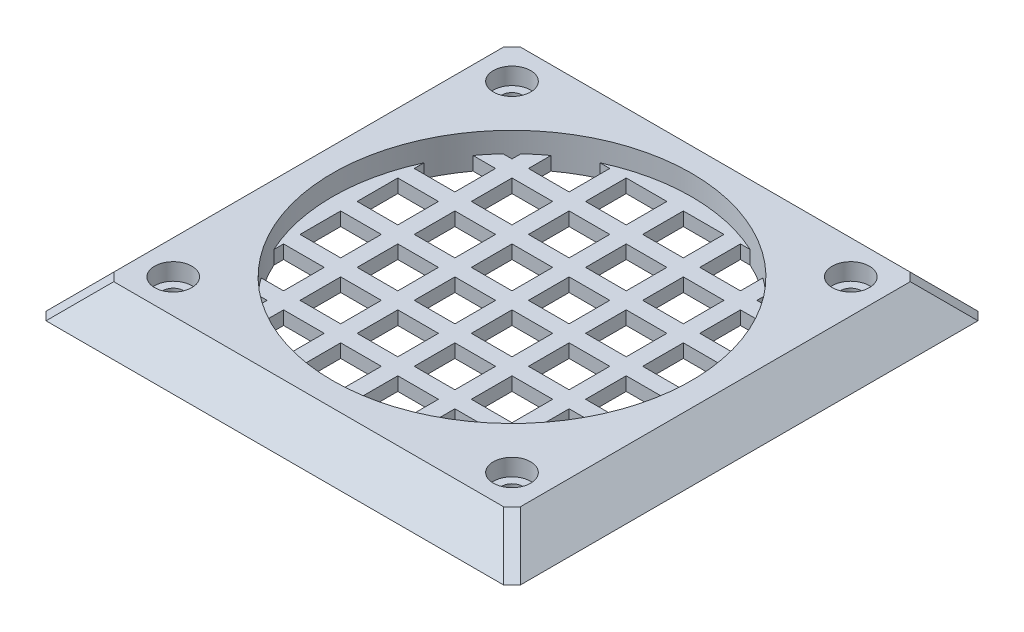
SolidWorks part; units mm, degrees
ref_plane "Front Plane" through (0, 0, 0) normal (0, 0, 1) x (1, 0, 0)
ref_plane "Top Plane" through (0, 0, 0) normal (0, 1, 0) x (1, 0, 0)
ref_plane "Right Plane" through (0, 0, 0) normal (1, 0, 0) x (0, 0, -1)
sketch "Sketch4" plane through (0, 0, 0) normal (0, 1, 0) x (1, 0, 0)
  line L1 (-57.895, 65.3251) -> (12.105, 65.3251)
  line L2 (-57.895, 65.3251) -> (-57.895, -4.6749)
  line L3 (-57.895, -4.6749) -> (12.105, -4.6749)
  line L4 (12.105, 65.3251) -> (12.105, -4.6749)
  dimension "D1" = 70
  dimension "D2" = 70
sketch "Sketch5" plane through (0, 0, 0) normal (0, 1, 0) x (1, 0, 0)
  line L0 (12.105, 65.3251) -> (12.105, -4.6749) construction
  line L1 (-57.895, 65.3251) -> (12.105, 65.3251) construction
  circle A0 centre (-22.895, 30.3251) radius 26.5
  dimension "D1" = 35
  dimension "D2" = 35
  dimension "D3" = 53
extrude "Boss-Extrude2" add sketch "Sketch4" against normal blind 5
extrude "Cut-Extrude3" cut sketch "Sketch5" against normal blind 3
chamfer "Chamfer2" distance 5 angle 45 1 edges at (12.105, 0, -30.3251)
chamfer "Chamfer3" distance 5 angle 45 1 edges at (-25.395, 0, -65.3251)
chamfer "Chamfer4" distance 5 angle 45 2 edges at (-25.395, 0, 4.6749) (-57.895, 0, -27.8251)
sketch "Sketch8" plane through (0, -3, 0) normal (0, 1, 0) x (1, 0, 0)
  line L0 (-49.395, 56.8251) -> (-46.9664, 56.8251)
  line L1 (-46.9664, 56.8251) -> (-46.9664, 54.3966)
  line L2 (-38.5379, 54.3966) -> (-38.5379, 48.3966)
  line L3 (-46.9664, 54.3966) -> (-40.9664, 54.3966)
  line L4 (-46.9664, 54.3966) -> (-46.9664, 48.3966)
  line L5 (-46.9664, 48.3966) -> (-40.9664, 48.3966)
  line L6 (-40.9664, 54.3966) -> (-40.9664, 48.3966)
  line L7 (-38.5379, 54.3966) -> (-32.5379, 54.3966)
  line L8 (-32.5379, 54.3966) -> (-32.5379, 48.3966)
  line L9 (-38.5379, 48.3966) -> (-32.5379, 48.3966)
  line L10 (-30.1093, 54.3966) -> (-30.1093, 48.3966)
  line L11 (-30.1093, 54.3966) -> (-24.1093, 54.3966)
  line L12 (-24.1093, 54.3966) -> (-24.1093, 48.3966)
  line L13 (-30.1093, 48.3966) -> (-24.1093, 48.3966)
  line L14 (-21.6807, 54.3966) -> (-21.6807, 48.3966)
  line L15 (-21.6807, 54.3966) -> (-15.6807, 54.3966)
  line L16 (-15.6807, 54.3966) -> (-15.6807, 48.3966)
  line L17 (-21.6807, 48.3966) -> (-15.6807, 48.3966)
  line L18 (-13.2522, 54.3966) -> (-13.2522, 48.3966)
  line L19 (-13.2522, 54.3966) -> (-7.2522, 54.3966)
  line L20 (-7.2522, 54.3966) -> (-7.2522, 48.3966)
  line L21 (-13.2522, 48.3966) -> (-7.2522, 48.3966)
  line L22 (-4.8236, 54.3966) -> (-4.8236, 48.3966)
  line L23 (-4.8236, 54.3966) -> (1.1764, 54.3966)
  line L24 (1.1764, 54.3966) -> (1.1764, 48.3966)
  line L25 (-4.8236, 48.3966) -> (1.1764, 48.3966)
  line L26 (-38.5379, 45.968) -> (-38.5379, 39.968)
  line L27 (-38.5379, 45.968) -> (-32.5379, 45.968)
  line L28 (-32.5379, 45.968) -> (-32.5379, 39.968)
  line L29 (-38.5379, 39.968) -> (-32.5379, 39.968)
  line L30 (-30.1093, 45.968) -> (-30.1093, 39.968)
  line L31 (-30.1093, 45.968) -> (-24.1093, 45.968)
  line L32 (-24.1093, 45.968) -> (-24.1093, 39.968)
  line L33 (-30.1093, 39.968) -> (-24.1093, 39.968)
  line L34 (-21.6807, 45.968) -> (-21.6807, 39.968)
  line L35 (-21.6807, 45.968) -> (-15.6807, 45.968)
  line L36 (-15.6807, 45.968) -> (-15.6807, 39.968)
  line L37 (-21.6807, 39.968) -> (-15.6807, 39.968)
  line L38 (-13.2522, 45.968) -> (-13.2522, 39.968)
  line L39 (-13.2522, 45.968) -> (-7.2522, 45.968)
  line L40 (-7.2522, 45.968) -> (-7.2522, 39.968)
  line L41 (-13.2522, 39.968) -> (-7.2522, 39.968)
  line L42 (-4.8236, 45.968) -> (-4.8236, 39.968)
  line L43 (-4.8236, 45.968) -> (1.1764, 45.968)
  line L44 (1.1764, 45.968) -> (1.1764, 39.968)
  line L45 (-4.8236, 39.968) -> (1.1764, 39.968)
  line L46 (-38.5379, 37.5394) -> (-38.5379, 31.5394)
  line L47 (-38.5379, 37.5394) -> (-32.5379, 37.5394)
  line L48 (-32.5379, 37.5394) -> (-32.5379, 31.5394)
  line L49 (-38.5379, 31.5394) -> (-32.5379, 31.5394)
  line L50 (-30.1093, 37.5394) -> (-30.1093, 31.5394)
  line L51 (-30.1093, 37.5394) -> (-24.1093, 37.5394)
  line L52 (-24.1093, 37.5394) -> (-24.1093, 31.5394)
  line L53 (-30.1093, 31.5394) -> (-24.1093, 31.5394)
  line L54 (-21.6807, 37.5394) -> (-21.6807, 31.5394)
  line L55 (-21.6807, 37.5394) -> (-15.6807, 37.5394)
  line L56 (-15.6807, 37.5394) -> (-15.6807, 31.5394)
  line L57 (-21.6807, 31.5394) -> (-15.6807, 31.5394)
  line L58 (-13.2522, 37.5394) -> (-13.2522, 31.5394)
  line L59 (-13.2522, 37.5394) -> (-7.2522, 37.5394)
  line L60 (-7.2522, 37.5394) -> (-7.2522, 31.5394)
  line L61 (-13.2522, 31.5394) -> (-7.2522, 31.5394)
  line L62 (-4.8236, 37.5394) -> (-4.8236, 31.5394)
  line L63 (-4.8236, 37.5394) -> (1.1764, 37.5394)
  line L64 (1.1764, 37.5394) -> (1.1764, 31.5394)
  line L65 (-4.8236, 31.5394) -> (1.1764, 31.5394)
  line L66 (-38.5379, 29.1108) -> (-38.5379, 23.1108)
  line L67 (-38.5379, 29.1108) -> (-32.5379, 29.1108)
  line L68 (-32.5379, 29.1108) -> (-32.5379, 23.1108)
  line L69 (-38.5379, 23.1108) -> (-32.5379, 23.1108)
  line L70 (-30.1093, 29.1108) -> (-30.1093, 23.1108)
  line L71 (-30.1093, 29.1108) -> (-24.1093, 29.1108)
  line L72 (-24.1093, 29.1108) -> (-24.1093, 23.1108)
  line L73 (-30.1093, 23.1108) -> (-24.1093, 23.1108)
  line L74 (-21.6807, 29.1108) -> (-21.6807, 23.1108)
  line L75 (-21.6807, 29.1108) -> (-15.6807, 29.1108)
  line L76 (-15.6807, 29.1108) -> (-15.6807, 23.1108)
  line L77 (-21.6807, 23.1108) -> (-15.6807, 23.1108)
  line L78 (-13.2522, 29.1108) -> (-13.2522, 23.1108)
  line L79 (-13.2522, 29.1108) -> (-7.2522, 29.1108)
  line L80 (-7.2522, 29.1108) -> (-7.2522, 23.1108)
  line L81 (-13.2522, 23.1108) -> (-7.2522, 23.1108)
  line L82 (-4.8236, 29.1108) -> (-4.8236, 23.1108)
  line L83 (-4.8236, 29.1108) -> (1.1764, 29.1108)
  line L84 (1.1764, 29.1108) -> (1.1764, 23.1108)
  line L85 (-4.8236, 23.1108) -> (1.1764, 23.1108)
  line L86 (-38.5379, 20.6823) -> (-38.5379, 14.6823)
  line L87 (-38.5379, 20.6823) -> (-32.5379, 20.6823)
  line L88 (-32.5379, 20.6823) -> (-32.5379, 14.6823)
  line L89 (-38.5379, 14.6823) -> (-32.5379, 14.6823)
  line L90 (-30.1093, 20.6823) -> (-30.1093, 14.6823)
  line L91 (-30.1093, 20.6823) -> (-24.1093, 20.6823)
  line L92 (-24.1093, 20.6823) -> (-24.1093, 14.6823)
  line L93 (-30.1093, 14.6823) -> (-24.1093, 14.6823)
  line L94 (-21.6807, 20.6823) -> (-21.6807, 14.6823)
  line L95 (-21.6807, 20.6823) -> (-15.6807, 20.6823)
  line L96 (-15.6807, 20.6823) -> (-15.6807, 14.6823)
  line L97 (-21.6807, 14.6823) -> (-15.6807, 14.6823)
  line L98 (-13.2522, 20.6823) -> (-13.2522, 14.6823)
  line L99 (-13.2522, 20.6823) -> (-7.2522, 20.6823)
  line L100 (-7.2522, 20.6823) -> (-7.2522, 14.6823)
  line L101 (-13.2522, 14.6823) -> (-7.2522, 14.6823)
  line L102 (-4.8236, 20.6823) -> (-4.8236, 14.6823)
  line L103 (-4.8236, 20.6823) -> (1.1764, 20.6823)
  line L104 (1.1764, 20.6823) -> (1.1764, 14.6823)
  line L105 (-4.8236, 14.6823) -> (1.1764, 14.6823)
  line L106 (-38.5379, 12.2537) -> (-38.5379, 6.2537)
  line L107 (-38.5379, 12.2537) -> (-32.5379, 12.2537)
  line L108 (-32.5379, 12.2537) -> (-32.5379, 6.2537)
  line L109 (-38.5379, 6.2537) -> (-32.5379, 6.2537)
  line L110 (-30.1093, 12.2537) -> (-30.1093, 6.2537)
  line L111 (-30.1093, 12.2537) -> (-24.1093, 12.2537)
  line L112 (-24.1093, 12.2537) -> (-24.1093, 6.2537)
  line L113 (-30.1093, 6.2537) -> (-24.1093, 6.2537)
  line L114 (-21.6807, 12.2537) -> (-21.6807, 6.2537)
  line L115 (-21.6807, 12.2537) -> (-15.6807, 12.2537)
  line L116 (-15.6807, 12.2537) -> (-15.6807, 6.2537)
  line L117 (-21.6807, 6.2537) -> (-15.6807, 6.2537)
  line L118 (-13.2522, 12.2537) -> (-13.2522, 6.2537)
  line L119 (-13.2522, 12.2537) -> (-7.2522, 12.2537)
  line L120 (-7.2522, 12.2537) -> (-7.2522, 6.2537)
  line L121 (-13.2522, 6.2537) -> (-7.2522, 6.2537)
  line L122 (-4.8236, 12.2537) -> (-4.8236, 6.2537)
  line L123 (-4.8236, 12.2537) -> (1.1764, 12.2537)
  line L124 (1.1764, 12.2537) -> (1.1764, 6.2537)
  line L125 (-4.8236, 6.2537) -> (1.1764, 6.2537)
  line L126 (-46.9664, 45.968) -> (-46.9664, 39.968)
  line L127 (-46.9664, 45.968) -> (-40.9664, 45.968)
  line L128 (-40.9664, 45.968) -> (-40.9664, 39.968)
  line L129 (-46.9664, 39.968) -> (-40.9664, 39.968)
  line L130 (-46.9664, 37.5394) -> (-46.9664, 31.5394)
  line L131 (-46.9664, 37.5394) -> (-40.9664, 37.5394)
  line L132 (-40.9664, 37.5394) -> (-40.9664, 31.5394)
  line L133 (-46.9664, 31.5394) -> (-40.9664, 31.5394)
  line L134 (-46.9664, 29.1108) -> (-46.9664, 23.1108)
  line L135 (-46.9664, 29.1108) -> (-40.9664, 29.1108)
  line L136 (-40.9664, 29.1108) -> (-40.9664, 23.1108)
  line L137 (-46.9664, 23.1108) -> (-40.9664, 23.1108)
  line L138 (-46.9664, 20.6823) -> (-46.9664, 14.6823)
  line L139 (-46.9664, 20.6823) -> (-40.9664, 20.6823)
  line L140 (-40.9664, 20.6823) -> (-40.9664, 14.6823)
  line L141 (-46.9664, 14.6823) -> (-40.9664, 14.6823)
  line L142 (-46.9664, 12.2537) -> (-46.9664, 6.2537)
  line L143 (-46.9664, 12.2537) -> (-40.9664, 12.2537)
  line L144 (-40.9664, 12.2537) -> (-40.9664, 6.2537)
  line L145 (-46.9664, 6.2537) -> (-40.9664, 6.2537)
  circle M39 centre (-22.895, 30.3251) radius 26.5
  dimension "D1" = 6
  dimension "D2" = 6
  dimension "D3" = 6
  dimension "D4" = 6
extrude "Cut-Extrude5" cut sketch "Sketch8" against normal up to surface (2 mm away) contours L6 L5 M39 | L2 L9 L8 L7 M39 | L10 L13 L12 L11 | L14 L17 L16 L15 | L18 L21 L20 L19 M39 | L22 L25 M39 | L42 L45 L44 L43 M39 | L38 L41 L40 L39 | L34 L37 L36 L35 | L30 L33 L32 L31 | L26 L29 L28 L27 | L126 L129 L128 L127 M39 | L130 L133 L132 L131 | L46 L49 L48 L47 | L50 L53 L52 L51 | L54 L57 L56 L55 | L58 L61 L60 L59 | L62 L65 L64 L63 | L82 L85 L84 L83 | L78 L81 L80 L79 | L74 L77 L76 L75 | L70 L73 L72 L71 | L66 L69 L68 L67 | L134 L137 L136 L135 | L141 L140 L139 L138 M39 | L86 L89 L88 L87 | L90 L93 L92 L91 | L94 L97 L96 L95 | L98 L101 L100 L99 | L102 L105 L104 L103 M39 | L123 L122 M39 | L118 L121 L120 L119 M39 | L114 L117 L116 L115 | L110 L113 L112 L111 | L109 L108 L107 L106 M39 | L144 L143 M39 region at (-35.2513, -3, -50.9986) region at (-41.4085, -3, -48.8386) region at (-10.5387, -3, -50.9986) region at (-43.5684, -3, -42.6814) region at (-4.3815, -3, -48.8386) region at (-43.5684, -3, -17.9688) region at (-2.2216, -3, -42.6814) region at (-41.4085, -3, -11.8117) region at (-2.2216, -3, -17.9688) region at (-35.2513, -3, -9.6517) region at (-4.3815, -3, -11.8117) region at (-10.5387, -3, -9.6517) region at (-27.1093, -3, -51.3966) region at (-18.6807, -3, -51.3966) region at (-35.5379, -3, -42.968) region at (-27.1093, -3, -42.968) region at (-18.6807, -3, -42.968) region at (-10.2522, -3, -42.968) region at (-35.5379, -3, -34.5394) region at (-27.1093, -3, -34.5394) region at (-18.6807, -3, -34.5394) region at (-10.2522, -3, -34.5394) region at (-1.8236, -3, -34.5394) region at (-35.5379, -3, -26.1108) region at (-27.1093, -3, -26.1108) region at (-18.6807, -3, -26.1108) region at (-10.2522, -3, -26.1108) region at (-1.8236, -3, -26.1108) region at (-35.5379, -3, -17.6823) region at (-27.1093, -3, -17.6823) region at (-18.6807, -3, -17.6823) region at (-10.2522, -3, -17.6823) region at (-27.1093, -3, -9.2537) region at (-18.6807, -3, -9.2537) region at (-43.9664, -3, -34.5394) region at (-43.9664, -3, -26.1108) up to face at (-22.895, -5, -30.3251)
chamfer "Chamfer5" distance 1 angle 30 4 edges at (-55.395, -2.5, 2.1749) (9.605, -2.5, 2.1749) (9.605, -2.5, -62.8251) (-55.395, -2.5, -62.8251) first distance on face at (-55.395, -2.5, -30.3251) first distance on face at (9.605, -2.5, -30.3251)
sketch "Sketch9" plane through (0, 0, 0) normal (0, 1, 0) x (1, 0, 0)
  line L1 (-47.895, 5.3251) -> (2.105, 5.3251)
  line L2 (-47.895, 5.3251) -> (-47.895, 55.3251)
  line L3 (-47.895, 55.3251) -> (2.105, 55.3251)
  line L4 (2.105, 5.3251) -> (2.105, 55.3251)
  line L5 (-47.895, 5.3251) -> (2.105, 55.3251) construction
  line L6 (-47.895, 55.3251) -> (2.105, 5.3251) construction
  circle A0 centre (-47.895, 55.3251) radius 1.5
  circle A1 centre (2.105, 55.3251) radius 1.5
  circle A2 centre (2.105, 5.3251) radius 1.5
  circle A3 centre (-47.895, 5.3251) radius 1.5
  circle A4 centre (-47.895, 55.3251) radius 2.75
  circle A5 centre (2.105, 55.3251) radius 2.75
  circle A6 centre (2.105, 5.3251) radius 2.75
  circle A7 centre (-47.895, 5.3251) radius 2.75
  point P0 (-22.895, 30.3251)
  dimension "D1" = 50
  dimension "D2" = 50
extrude "Cut-Extrude6" cut sketch "Sketch9" against normal up to surface (5 mm away) contours A0 | A1 | A2 | A3 up to face at (-1.8236, -5, -34.5394)
extrude "Cut-Extrude7" cut sketch "Sketch9<3>" against normal blind 2.5 contours A4 | A5 | A6 | A7
sketch "Sketch9<3>" plane through (0, 0, 0) normal (0, 1, 0) x (1, 0, 0) same geometry as "Sketch9"
